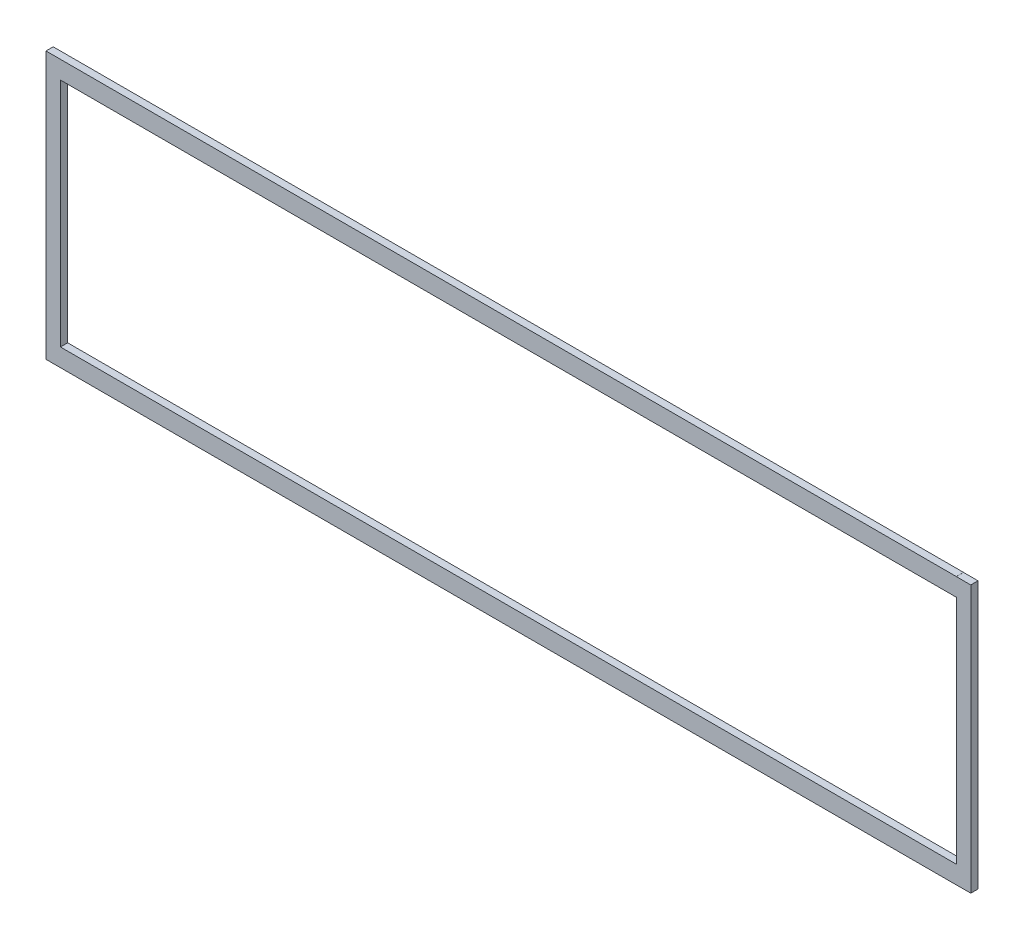
SolidWorks part; units mm, degrees
ref_plane "Front Plane" through (0, 0, 0) normal (0, 0, 1) x (1, 0, 0)
ref_plane "Top Plane" through (0, 0, 0) normal (0, 1, 0) x (1, 0, 0)
ref_plane "Right Plane" through (0, 0, 0) normal (1, 0, 0) x (0, 0, -1)
sketch "Sketch1" plane through (0, 0, 0) normal (0, 0, 1) x (1, 0, 0)
  line L0 (0, 58.6835) -> (406.4, 58.6835) construction
  line L1 (0, 0) -> (400.05, 0)
  line L2 (0, 0) -> (0, 117.3671)
  line L3 (0, 117.3671) -> (400.05, 117.3671)
  line L4 (406.4, 0) -> (406.4, 117.3671)
  line L6 (400.05, 117.3671) -> (400.05, 117.3417)
  line L7 (400.05, 117.3417) -> (406.4, 117.3417)
  line L8 (406.4, 117.3671) -> (406.4, 117.3417)
  line L9 (406.4, 0) -> (406.4, 0.0254)
  line L10 (400.05, 0.0254) -> (406.4, 0.0254)
  line L11 (400.05, 0) -> (400.05, 0.0254)
  line L13 (6.35, 109.4835) -> (400.05, 109.4835)
  line L14 (6.35, 109.4835) -> (6.35, 7.8835)
  line L15 (6.35, 7.8835) -> (400.05, 7.8835)
  line L16 (400.05, 109.4835) -> (400.05, 7.8835)
  point P17 (6.35, 58.6835)
  dimension "D1" = 406.4
  dimension "D2" = 117.3671
  dimension "D3" = 117.3163
  dimension "D4" = 6.35
  dimension "D5" = 6.35
  dimension "D6" = 6.35
  dimension "D7" = 101.6
extrude "Boss-Extrude1" add sketch "Sketch1" along normal blind 3.175 contours L0 L2 L1 L11 L10 L4 L16 L15 L14 | L2 L0 L14 L13 L16 L4 L7 L6 L3 region at (4.1062, 88.0253, 0) region at (3.175, 54.5774, 0)
equation "\"ROADWIDTH\"=4.62075"
equation "\"TABWIDTH\"=4.61875"
equation "\"D2@Sketch1\"=\"ROADWIDTH\""
equation "\"D3@Sketch1\"=\"TABWIDTH\""
